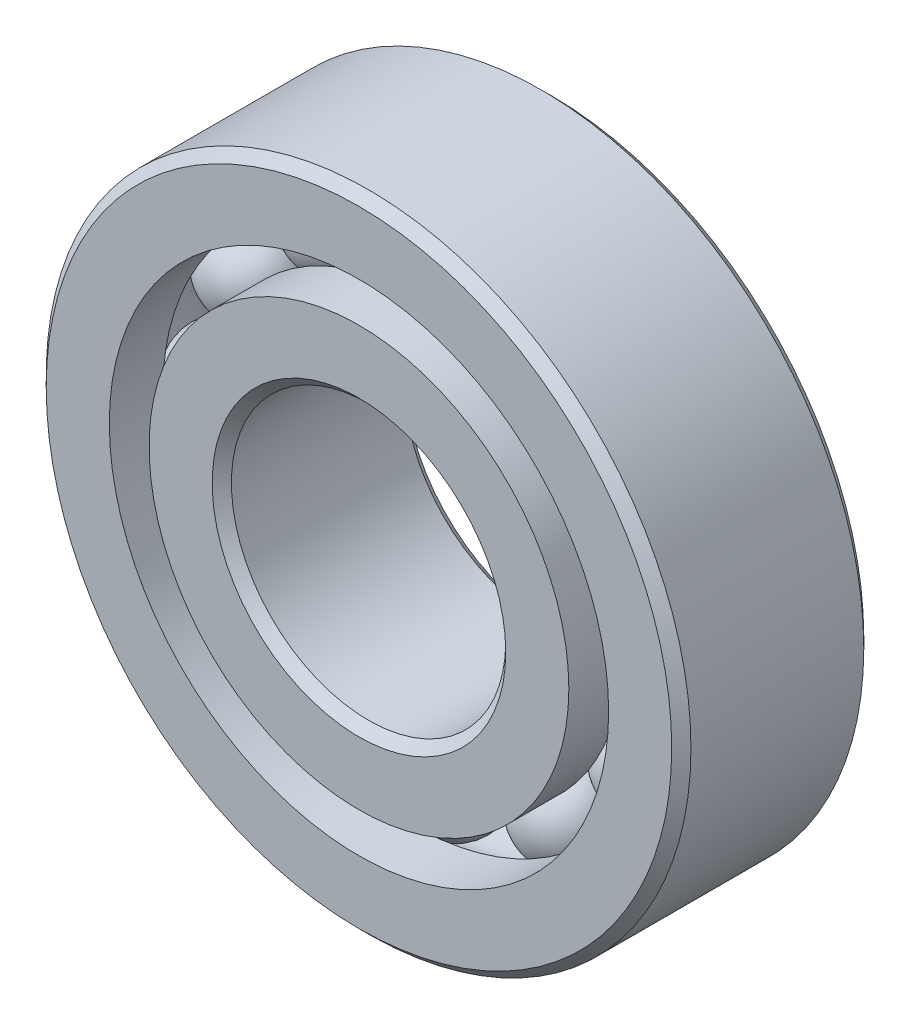
SolidWorks part; units mm, degrees
ref_plane "Front Plane" through (0, 0, 0) normal (0, 0, 1) x (1, 0, 0)
ref_plane "Top Plane" through (0, 0, 0) normal (0, 1, 0) x (1, 0, 0)
ref_plane "Right Plane" through (0, 0, 0) normal (1, 0, 0) x (0, 0, -1)
sketch "Sketch1" plane through (0, 0, 0) normal (1, 0, 0) x (0, 0, -1)
  line L0 (-7, 0) -> (7, 0) construction
  line L1 (0, 23.5) -> (0, -23.5) construction
  line L2 (6.3, 23.5) -> (-6.3, 23.5)
  line L3 (-6.3, 23.5) -> (-7, 22.8)
  line L4 (-7, 22.8) -> (-7, 18.2005)
  line L5 (-7, 18.2005) -> (-3.1111, 18.2005)
  line L6 (7, 18.2005) -> (3.1111, 18.2005)
  line L7 (7, 22.8) -> (7, 18.2005)
  line L8 (6.3, 23.5) -> (7, 22.8)
  line L9 (0, 23.5) -> (0, 16.75) construction
  line L10 (0, 16.75) -> (0, 10) construction
  arc A0 (-3.1111, 18.2005) -> (3.1111, 18.2005) centre (0, 16.75) cw
  point P14 (0, 10)
  dimension "Width" = 14
  dimension "OD" = 47
  dimension "D1" = 45
  dimension "D2" = 0.7
  dimension "Shaft Dia" = 20
  dimension "D3" = 6.2222
  dimension "D4" = 1.4505
revolve "Revolve1" add sketch "Sketch1" angle 360 about L0
sketch "Sketch3" plane through (0, 0, 0) normal (1, 0, 0) x (0, 0, -1)
  line L0 (-7, 15.2995) -> (-3.1111, 15.2995)
  line L1 (0, 23.5) -> (0, -23.5) construction
  line L2 (-7, 22.8) -> (-7, 18.2005) construction
  line L3 (-7, 15.2995) -> (-7, 10.7)
  line L4 (-6.3, 23.5) -> (-7, 22.8) construction
  line L5 (-7, 10.7) -> (-6.3, 10)
  line L6 (-6.3, 10) -> (6.3, 10)
  line L7 (6.3, 23.5) -> (6.3, -23.5) construction
  line L8 (6.3, 10) -> (7, 10.7)
  line L9 (7, -22.8) -> (7, 22.8) construction
  line L10 (7, 10.7) -> (7, 15.2995)
  line L11 (7, 15.2995) -> (3.1111, 15.2995)
  line L13 (6.3, 23.5) -> (7, 22.8) construction
  arc A0 (3.1111, 18.2005) -> (-3.1111, 18.2005) centre (0, 16.75) ccw construction
  arc A1 (3.1111, 15.2995) -> (-3.1111, 15.2995) centre (0, 16.75) cw
revolve "Revolve3" add sketch "Sketch3" angle 360 about L0
sketch "Sketch4" plane through (0, 0, 0) normal (1, 0, 0) x (0, 0, -1)
  line L0 (-3.4327, 16.75) -> (3.4327, 16.75)
  arc A2 (-3.4327, 16.75) -> (3.4327, 16.75) centre (0, 16.75) cw
  arc A3 (3.1111, 18.2005) -> (-3.1111, 18.2005) centre (0, 16.75) ccw construction
revolve "Revolve4" add sketch "Sketch4" angle 360 about L0
ref_axis "Axis1" through (0, 0, -7) along (0, 0, 1)
pattern_circular "CirPattern1" count 12 over 360 about axis through (0, 0, -7) along (0, 0, 1) of bodies 104
sketch "Sketch5" plane through (0, 0, 0) normal (1, 0, 0) x (0, 0, -1)
  line L0 (-7, 18.2005) -> (-3.1111, 18.2005) construction
  line L1 (-6.65, 18.2005) -> (-3.4327, 18.2005)
  line L2 (-6.65, 18.2005) -> (-6.65, 15.2995)
  line L3 (-6.65, 15.2995) -> (-3.4327, 15.2995)
  line L4 (-3.4327, 18.2005) -> (-3.4327, 15.2995)
  line L5 (-7, 15.2995) -> (-3.1111, 15.2995) construction
  line L6 (7, 18.2005) -> (3.1111, 18.2005) construction
  line L7 (6.65, 18.2005) -> (3.4327, 18.2005)
  line L8 (6.65, 18.2005) -> (6.65, 15.2995)
  line L9 (6.65, 15.2995) -> (3.4327, 15.2995)
  line L10 (3.4327, 18.2005) -> (3.4327, 15.2995)
  line L11 (7, 15.2995) -> (3.1111, 15.2995) construction
  line L12 (-6.3, 23.5) -> (-7, 22.8) construction
  point P18 (-6.65, 23.15)
revolve "Revolve5" [suppressed] add sketch "Sketch5" angle 360 about L0 other way angle 360
equation "\"D2@Sketch1\" = \"Width@Sketch1\"*.05"
equation "\"D3@Sketch1\" = \"Width@Sketch1\"/2.25"
equation "\"D4@Sketch1\" = (((\"OD@Sketch1\"-\"Width@Sketch1\")/2)/3.25)/3.5"
equation "\"D2@CirPattern1\" = 360/\"Balls@CirPattern1\""
